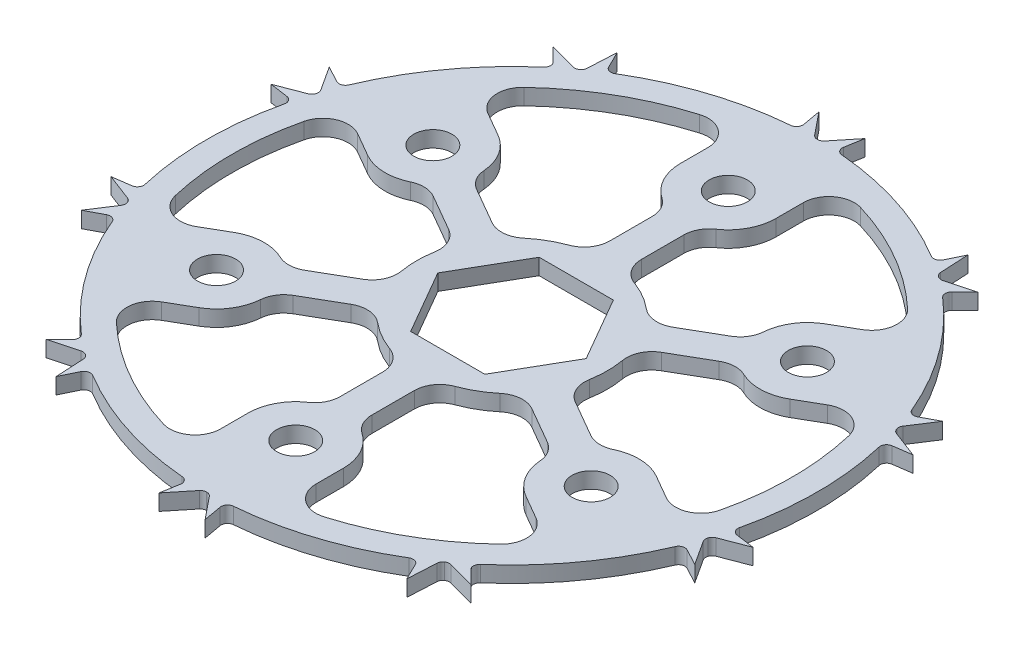
SolidWorks part; units mm, degrees
note: '?' marks a value the reader was unsure of.
material "Commercially Pure CP-Ti UNS R50700  Grade 4 (SS)"
ref_plane "Front Plane" through (0, 0, 0) normal (0, 0, 1) x (1, 0, 0)
ref_plane "Top Plane" through (0, 0, 0) normal (0, 1, 0) x (1, 0, 0)
ref_plane "Right Plane" through (0, 0, 0) normal (1, 0, 0) x (0, 0, -1)
other "Bounding Box"
ref_plane "Default Plane" through (13.8565, 3.175, 6.7999) normal (0, -1, 0) x (-1, 0, 0)
sketch "Sketch1" plane through (0, 0, 0) normal (0, 1, 0) x (1, 0, 0)
  line L0 (22.4506, -22.4506) -> (0, 0) construction
  line L1 (0, 0) -> (22.4506, 22.4506) construction
  line L2 (0, 0) -> (0, 31.75) construction
  circle A0 centre (0, 0) radius 31.75
  point P3 (0, 31.75)
  point P4 (31.75, 0)
  point P5 (-31.75, 0)
  point P6 (0, -31.75)
  point P7 (22.4506, 22.4506)
  point P8 (22.4506, -22.4506)
  dimension "D1" = 63.5
  dimension "D2" = 45
extrude "Boss-Extrude1" add sketch "Sketch1" along normal mid plane 15.24
ref_plane "Plane2" through (-31.75, 0, 0) normal (-1, 0, 0) x (0, 0, 1)
sketch "Sketch9" plane through (-31.75, 0, 0) normal (-1, 0, 0) x (0, 0, 1)
  line L0 (-0.635, -7.62) -> (0.635, -7.62)
  line L1 (-31.75, -7.62) -> (31.75, -7.62) construction
  line L2 (0.635, -7.62) -> (0.635, 0)
  line L3 (31.75, 7.62) -> (-31.75, 7.62) construction
  line L5 (-0.635, 0) -> (-0.635, -7.62)
  line L6 (0.635, -7.62) -> (0, -7.62) construction
  line L7 (0, -7.62) -> (0, 7.62) construction
  line L9 (-0.635, 0) -> (0.635, 0) construction
  line L10 (0.635, 0) -> (0.635, 7.62)
  line L11 (0.635, 7.62) -> (-0.635, 7.62)
  line L13 (-0.635, 7.62) -> (-0.635, 0)
  point P14 (0, 0)
  dimension "D2" = 1.27
extrude "Cut-Extrude4" cut sketch "Sketch9" against normal blind 0.635
sketch "Sketch4" plane through (0, 0, 0) normal (0, 0, 1) x (1, 0, 0)
  line L0 (-31.75, -7.62) -> (-29.21, -7.62)
  line L1 (-31.7436, -7.62) -> (31.75, -7.62) construction
  line L4 (31.75, 7.62) -> (-31.7436, 7.62) construction
  line L5 (-29.21, 7.62) -> (-31.75, 7.62)
  line L6 (-31.75, 7.62) -> (-31.75, -7.62)
  line L7 (-6.35, 0) -> (0, 0) construction
  line L8 (-29.21, -7.62) -> (-29.21, -6.0325)
  line L9 (-29.21, -6.0325) -> (-6.35, 0)
  line L10 (-6.35, 0) -> (-29.21, 6.0325)
  line L11 (-29.21, 6.0325) -> (-29.21, 7.62)
  point P17 (-31.75, 0)
  dimension "D1" = 2.54
  dimension "D2" = 25.4
  dimension "D3" = 1.5875
pattern_circular "CirPattern2" count 20 over 360 about axis through (0, 0, 0) along (0, 1, 0) of "Cut-Extrude4"
ref_axis "Axis1" through (0, -9.0805, 0) along (0, 1, 0)
sketch "Sketch3" plane through (0, 7.62, 0) normal (0, 1, 0) x (1, 0, 0)
  line L0 (0, 0) -> (0, 21.59) construction
  line L1 (0, 21.59) -> (0, 31.75) construction
  circle A0 centre (0, 21.59) radius 1.397
  circle A1 centre (0, 0) radius 31.75 construction
  circle A2 centre (0, 21.59) radius 4.7625
  dimension "D2" = 2.794
  dimension "D3" = 9.525
  dimension "D1" = 10.16
move or copy body "Body-Move/Copy1" [suppressed] parameters "D1"=0, "D2"=0, "D3"=0
revolve "Cut-Revolve2" cut sketch "Sketch4" angle 360 about axis through (0, -9.0805, 0) along (0, 1, 0)
sketch "Sketch5" plane through (0, 7.62, 0) normal (0, 1, 0) x (1, 0, 0)
  circle A0 centre (0, 21.59) radius 4.7625
  circle A1 centre (0, 21.59) radius 1.397 construction
  circle A3 centre (0, 21.59) radius 1.397
  circle A4 centre (0, 21.59) radius 4.7625 construction
extrude "Boss-Extrude2" add sketch "Sketch5" against normal through all
sketch "Sketch12" plane through (0, 7.62, 0) normal (0, 1, 0) x (1, 0, 0)
  line L0 (-18.6975, 10.795) -> (0, 0) construction
  line L1 (-18.6975, -10.795) -> (-18.6975, 10.795) construction
  line L2 (-18.6975, 10.795) -> (0, 21.59) construction
  line L3 (-18.6975, -10.795) -> (0, 0) construction
  line L4 (0, 0) -> (0, 21.59) construction
  circle A0 centre (-18.6975, 10.795) radius 4.7625
  circle A1 centre (0, 21.59) radius 4.7625 construction
  dimension "D3" = 120
extrude "Boss-Extrude6" add sketch "Sketch12" against normal through all
sketch "Sketch17" plane through (0, 0, 0) normal (0, 1, 0) x (1, 0, 0)
  line L0 (0, 21.59) -> (0, 0) construction
  line L1 (0, 0) -> (-18.6975, 10.795) construction
  line L2 (0, 0) -> (-18.6975, -10.795) construction
  line L3 (-22.8219, -13.1763) -> (-25.2966, -14.605)
  line L4 (0, 26.3525) -> (0, 29.21)
  line L5 (-21.0787, -6.6706) -> (-18.9225, -5.4257)
  line L6 (-18.9225, 5.4257) -> (-21.0787, 6.6706)
  line L7 (-16.3162, 14.9194) -> (-14.16, 13.6745)
  line L8 (-4.7625, 21.59) -> (-4.7625, 19.1002)
  circle A0 centre (0, 21.59) radius 4.7625 construction
  circle A1 centre (-18.6975, 10.795) radius 4.7625 construction
  arc A2 (0, 26.3525) -> (-4.7625, 21.59) centre (0, 21.59) ccw
  arc A3 (-16.3162, 14.9194) -> (-21.0787, 6.6706) centre (-18.6975, 10.795) ccw
  arc A5 (-4.7625, 19.1002) -> (-14.16, 13.6745) centre (0, 0) ccw
  circle A6 centre (0, 21.59) radius 1.397 construction
  arc A7 (-21.0787, -6.6706) -> (-22.8219, -13.1763) centre (-18.6975, -10.795) ccw
  circle A8 centre (0, 0) radius 29.21 construction
  circle A9 centre (0, 21.59) radius 1.397
  circle A10 centre (0, 0) radius 29.21 construction
  arc A11 (0, 29.21) -> (-25.2966, -14.605) centre (0, 0) ccw
  arc A12 (-18.9225, 5.4257) -> (-18.9225, -5.4257) centre (0, 0) ccw
  circle A13 centre (-18.6975, 10.795) radius 1.397
  circle A15 centre (-18.6975, -10.795) radius 1.397
  dimension "D1" = 9.525
extrude "Cut-Extrude5" cut sketch "Sketch17" against normal through all both and the other way through all
pattern_circular "CirPattern1" count 3 over 360 about axis through (0, 0, 0) along (0, 1, 0) of "Boss-Extrude2", "Boss-Extrude6", "Cut-Extrude5"
sketch "Sketch18" plane through (0, -7.62, 0) normal (0, -1, 0) x (1, 0, 0)
  circle A0 centre (0, 0) radius 19.685 construction
  circle A1 centre (0, 0) radius 12.7
  arc A2 (-4.7625, 19.1002) -> (-14.16, 13.6745) centre (0, 0) ccw construction
  circle A3 centre (0, 0) radius 6.35 construction
  circle A4 centre (0, 0) radius 6.35 construction
  circle A5 centre (0, 0) radius 31.75 construction
  dimension "D1" = 19.05
extrude "Boss-Extrude9" add sketch "Sketch18" against normal through all
fillet "Fillet5" radius 1.27 2 edges at (0, -1.6757, -12.7) (0, 1.6757, 12.7)
sketch "Sketch24" plane through (0, -7.62, 0) normal (0, -1, 0) x (1, 0, 0)
  line L1 (3.6662, -6.35) -> (7.3323, 0)
  line L2 (7.3323, 0) -> (3.6662, 6.35)
  line L3 (3.6662, 6.35) -> (-3.6662, 6.35)
  line L4 (-3.6662, 6.35) -> (-7.3323, 0)
  line L5 (-7.3323, 0) -> (-3.6662, -6.35)
  line L6 (-3.6662, -6.35) -> (3.6662, -6.35)
  circle A0 centre (0, 0) radius 4 construction
  circle A1 centre (0, 0) radius 6.35 construction
  dimension "D1" = 8
  dimension "D2" = 12.7
extrude "Cut-Extrude7" cut sketch "Sketch24" against normal through all
combine bodies "Combine3" [suppressed] bodies to combine 116 167
delete or keep bodies "Body-Delete/Keep 4" [suppressed] type keep bodies bodies 117
sketch "Sketch7" [suppressed] plane through (0, -8.255, 0) normal (0, -1, 0) x (1, 0, 0)
  circle A0 centre (0, 0) radius 38.1
  circle A1 centre (0, 0) radius 31.75 construction
  dimension "D1" = 6.35
extrude "Boss-Extrude4" [suppressed] add sketch "Sketch7" against normal offset from surface (19.685 mm away) 3.175 separate body
combine bodies "Combine2" [suppressed] operation type? add bodies to combine 117 117
sketch "Sketch15" [suppressed] plane through (0, 0, 0) normal (1, 0, 0) x (0, 0, -1)
  line L0 (-38.1, -8.255) -> (-43.18, -13.335)
  line L1 (-43.18, -13.335) -> (-36.83, -13.335)
  line L2 (-36.83, -13.335) -> (-31.75, -8.255)
  line L3 (-31.75, -8.255) -> (-38.1, -8.255)
  dimension "D1" = 5.08
  dimension "D2" = 45
  dimension "D3" = 6.35
ref_axis "Axis2" [suppressed] through (0, -9.3002, 0) along (0, 1, 0)?
revolve "Revolve1" [suppressed] add sketch "Sketch15" angle 360 about axis through (0, -9.3002, 0) along (0, 1, 0)
fillet "Fillet4" [suppressed] radius 6.35
sketch "Sketch27" [suppressed] plane through (0, 11.43, 0) normal (0, 1, 0) x (1, 0, 0)
  line L0 (37.5671, 6.35) -> (44.45, 6.35)
  line L1 (44.45, -6.35) -> (37.5671, -6.35)
  line L2 (38.1, 0) -> (44.45, 0) construction
  circle A0 centre (44.45, 0) radius 1.905
  arc A1 (37.5671, -6.35) -> (37.5671, 6.35) centre (0, 0) ccw
  circle A2 centre (0, 0) radius 38.1 construction
  arc A3 (44.45, 6.35) -> (44.45, -6.35) centre (44.45, 0) cw
  dimension "D2" = 3.81
  dimension "D3" = 6.35
  dimension "D1" = 6.35
extrude "Boss-Extrude13" [suppressed] add sketch "Sketch27" against normal blind 9.525
pattern_circular "CirPattern7" [suppressed] count 3 over 360
split "Split1" [suppressed] bodies to split 124
sketch "Sketch19" [suppressed] plane through (0, 11.43, 0) normal (0, 1, 0) x (1, 0, 0)
  line L0 (-20.447, 35.4152) -> (-19.177, 33.2155)
  line L1 (-20.447, -35.4152) -> (-19.177, -33.2155)
  line L2 (-40.894, 0) -> (0, 0) construction
  arc A0 (-19.177, 33.2155) -> (-19.177, -33.2155) centre (0, 0) ccw
  circle A1 centre (0, 0) radius 38.1 construction
  arc A2 (-20.447, 35.4152) -> (-20.447, -35.4152) centre (0, 0) ccw
  dimension "D2" = 2.54
  dimension "D3" = 0.254
  dimension "D1" = 120
extrude "Boss-Extrude10" [suppressed] add sketch "Sketch19" against normal blind 6.35 separate body
sketch "Sketch21" [suppressed] plane through (0, 11.43, 0) normal (0, 1, 0) x (1, 0, 0)
  line L0 (-19.177, 33.2155) -> (-19.05, 32.9956)
  line L1 (-19.177, -33.2155) -> (-19.05, -32.9956)
  line L2 (-19.177, 33.2155) -> (-20.447, 35.4152) construction
  line L3 (-20.447, -35.4152) -> (-19.177, -33.2155) construction
  arc A1 (-19.177, 33.2155) -> (-19.177, -33.2155) centre (0, 0) ccw construction
  arc A2 (-19.05, 32.9956) -> (-19.05, -32.9956) centre (0, 0) ccw
  arc A3 (-19.177, 33.2155) -> (-19.177, -33.2155) centre (0, 0) ccw
  circle A4 centre (0, 0) radius 38.1 construction
extrude "Boss-Extrude11" [suppressed] add sketch "Sketch21" against normal blind 3.1496
pattern_circular "CirPattern6" [suppressed] count 3 over 360
combine bodies "Combine4" [suppressed] bodies to combine 137 137 135 134
chamfer "Chamfer4" [suppressed] distance 0.635 angle 45
delete or keep bodies "Body-Delete/Keep 1" [suppressed] type delete bodies bodies 133
delete or keep bodies "Body-Delete/Keep 2" [suppressed] type delete bodies bodies 121
mirror "Mirror1" [suppressed] about plane through (0, 0, 0) normal (1, 0, 0)
delete or keep bodies "Body-Delete/Keep 3" [suppressed] type delete bodies bodies 121
sketch "Sketch28" [suppressed] plane through (0, 8.255, 0) normal (0, -1, 0) x (1, 0, 0)
  circle A0 centre (0, 0) radius 15.24
  dimension "D1" = 30.48
extrude "Boss-Extrude14" [suppressed] add sketch "Sketch28" along normal blind 0.635
sketch "Sketch29" [suppressed] plane through (0, 7.62, 0) normal (0, -1, 0) x (1, 0, 0)
  circle A0 centre (0, 0) radius 9.144
  dimension "D1" = 18.288
extrude "Boss-Extrude15" [suppressed] add sketch "Sketch29" along normal blind 10.16
sketch "Sketch30" plane through (0, -7.62, 0) normal (0, -1, 0) x (1, 0, 0)
  circle A12 centre (0, 0) radius 30.48
  circle A13 centre (0, 0) radius 27.94
  circle A14 centre (0, 0) radius 31.75 construction
  dimension "D1" = 1.27
  dimension "D2" = 2.54
extrude "Boss-Extrude16" add sketch "Sketch30" along normal blind 1.6002 separate body
sketch "Sketch31" plane through (0, -9.2202, 0) normal (0, -1, 0) x (1, 0, 0)
  line L0 (-4.7625, 21.59) -> (-4.7625, 30.1056)
  line L1 (-4.7625, 30.1056) -> (4.7625, 30.1056)
  line L2 (4.7625, 30.1056) -> (4.7625, 21.59)
  line L3 (0, 0) -> (0, 21.59) construction
  line L5 (-1.5875, 17.0999) -> (1.5875, 17.0999) construction
  line L6 (-1.5875, 17.0999) -> (-1.5875, 7.62)
  line L7 (-1.5875, 7.62) -> (1.5875, 7.62)
  line L8 (1.5875, 17.0999) -> (1.5875, 7.62)
  line L9 (-1.5875, 17.0999) -> (1.5875, 7.62) construction
  line L10 (-1.5875, 7.62) -> (1.5875, 17.0999) construction
  arc A0 (-1.5875, 17.0999) -> (-4.7625, 21.59) centre (0, 21.59) cw
  circle A1 centre (0, 21.59) radius 1.905
  arc A2 (4.7625, 21.59) -> (1.5875, 17.0999) centre (0, 21.59) cw
  circle A3 centre (0, 21.59) radius 1.397 construction
  circle A4 centre (0, 0) radius 30.48 construction
  point P6 (0, 12.3599)
  dimension "D1" = 4.7625
  dimension "D2" = 3.81
  dimension "D3" = 7.62
  dimension "D4" = 3.175
extrude "Boss-Extrude17" add sketch "Sketch31" against normal up to surface (1.6002 mm away) up to face at (0, -7.62, -30.48)
sketch "Sketch33" plane through (0, -9.2202, 0) normal (0, -1, 0) x (1, 0, 0)
  line L1 (3.7028, -6.4135) -> (7.4057, 0)
  line L2 (7.4057, 0) -> (3.7028, 6.4135)
  line L3 (3.7028, 6.4135) -> (-3.7028, 6.4135)
  line L4 (-3.7028, 6.4135) -> (-7.4057, 0)
  line L5 (-7.4057, 0) -> (-3.7028, -6.4135)
  line L6 (-3.7028, -6.4135) -> (3.7028, -6.4135)
  circle A0 centre (0, 0) radius 6.4135 construction
  circle A1 centre (0, 0) radius 9.525
  dimension "D2" = 19.05
  dimension "D1" = 12.827
extrude "Boss-Extrude19" add sketch "Sketch33" against normal up to surface (1.6002 mm away) up to face at (0, -7.62, -30.48)
fillet "Fillet6" radius 2.54 2 edges at (4.7625, -8.4201, 27.5311) (-4.7625, -8.4201, 27.5311)
fillet "Fillet8" radius 2.54 4 edges at (1.5875, -8.4201, 9.3918) (1.5875, -8.4201, 17.0999) (-1.5875, -8.4201, 9.3918) (-1.5875, -8.4201, 17.0999)
pattern_circular "CirPattern8" count 6 over 360 about axis through (0, 0, 0) along (0, 1, 0) of "Boss-Extrude17", "Fillet6", "Fillet8"
sketch "Sketch32" plane through (0, -9.2202, 0) normal (0, -1, 0) x (1, 0, 0)
  line L0 (0, 0) -> (-2.3034, 32.9396) construction
  line L1 (2.3034, 32.9396) -> (0.3104, 30.4784)
  line L2 (0, 0) -> (0, 33.02) construction
  line L3 (-1.8597, 30.4232) -> (-2.3034, 32.9396)
  line L4 (-2.3034, 32.9396) -> (-0.3104, 30.4784)
  line L5 (-0.3104, 30.4784) -> (-1.8597, 30.4232)
  line L6 (1.8597, 30.4232) -> (2.3034, 32.9396)
  line L7 (0.3104, 30.4784) -> (1.8597, 30.4232)
  line L8 (-2.3034, 32.9396) -> (2.3034, 32.9396) construction
  circle A0 centre (0, 0) radius 30.48 construction
  circle A1 centre (0, 0) radius 33.02 construction
  circle A2 centre (0, 0) radius 31.75 construction
  dimension "D2" = 1.27
  dimension "D1" = 6
  dimension "D3" = 35
  dimension "D4" = 4
extrude "Boss-Extrude18" add sketch "Sketch32" against normal up to surface (1.6002 mm away) up to face at (17.5819, -7.62, 0)
fillet "Fillet7" radius 0.635 4 edges at (1.8597, -8.4201, 30.4232) (0.3104, -8.4201, 30.4784) (-0.3104, -8.4201, 30.4784) (-1.8597, -8.4201, 30.4232)
pattern_circular "CirPattern9" count 10 over 360 about axis through (0, 0, 0) along (0, 1, 0) of "Boss-Extrude18", "Fillet7"
delete or keep bodies "Body-Delete/Keep 5" bodies 185
